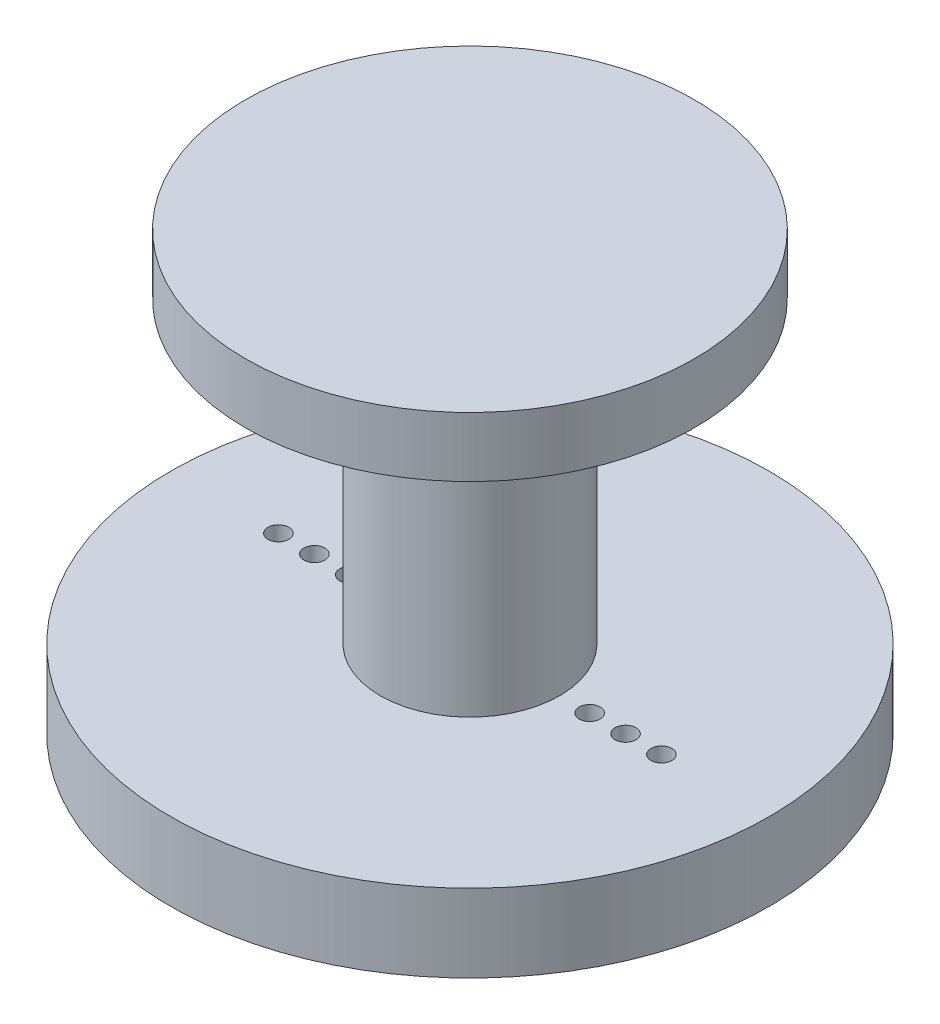
SolidWorks part; units mm, degrees
ref_plane "Front Plane" through (0, 0, 0) normal (0, 0, 1) x (1, 0, 0)
ref_plane "Top Plane" through (0, 0, 0) normal (0, 1, 0) x (1, 0, 0)
ref_plane "Right Plane" through (0, 0, 0) normal (1, 0, 0) x (0, 0, -1)
sketch "Sketch1" plane through (0, 0, 0) normal (0, 1, 0) x (1, 0, 0)
  circle A0 centre (0, 0) radius 25
  dimension "D1" = 50
extrude "Boss-Extrude1" add sketch "Sketch1" along normal blind 6.5 contours A0
sketch "Sketch8" plane through (0, 0, 0) normal (0, -1, 0) x (1, 0, 0)
  line L4 (0, 25) -> (0, -25) construction
  line L5 (-25, 0) -> (25, 0) construction
  circle A4 centre (0, 0) radius 25 construction
  arc A19 (2.8678, 6.2766) -> (8.1035, 4.0243) centre (-3.6427, -16.0687) cw
  arc A20 (8.1035, 4.0243) -> (17.4455, 2.5243) centre (-5.206, -108.7086) cw
  arc A21 (17.4455, 2.5243) -> (21, -0.4757) centre (17.8847, -0.5611) cw
  arc A22 (17.4455, -2.5243) -> (21, -0.4757) centre (18.0512, 0.5327) ccw
  arc A23 (2.8678, -6.2766) -> (8.1035, -4.0243) centre (-3.6427, 16.0687) ccw
  arc A24 (8.1035, -4.0243) -> (17.4455, -2.5243) centre (-5.206, 108.7086) ccw
  arc A25 (2.8678, 6.2766) -> (-2.8678, 6.2766) centre (0, 0) ccw
  arc A26 (-2.8678, -6.2766) -> (2.8678, -6.2766) centre (0, 0) ccw
  arc A27 (-2.8678, 6.2766) -> (-8.1035, 4.0243) centre (3.6427, -16.0687) ccw
  arc A28 (-8.1035, 4.0243) -> (-17.4455, 2.5243) centre (5.206, -108.7086) ccw
  arc A29 (-17.4455, 2.5243) -> (-21, -0.4757) centre (-17.8847, -0.5611) ccw
  arc A30 (-17.4455, -3.4757) -> (-21, -0.4757) centre (-17.8847, -0.3904) cw
  arc A31 (-8.1035, -4.0243) -> (-17.4455, -3.4757) centre (-6.1266, 109.4743) cw
  arc A32 (-2.8678, -6.2766) -> (-8.1035, -4.0243) centre (3.6427, 16.0687) cw
extrude "Horn Hole" cut sketch "Sketch8" against normal blind 2
sketch "Sketch9" plane through (0, 2, 0) normal (0, -1, 0) x (1, 0, 0)
  line L0 (0, 0) -> (7, 0) construction
  line L1 (0, 0) -> (0, -2.0664) construction
  circle A0 centre (7, 0) radius 0.875 construction
  circle A1 centre (10, 0) radius 0.875
  circle A8 centre (13, 0) radius 0.875
  circle A9 centre (16, 0) radius 0.875
  circle A10 centre (-7, 0) radius 0.875 construction
  circle A11 centre (-10, 0) radius 0.875
  circle A12 centre (-13, 0) radius 0.875
  circle A13 centre (-16, 0) radius 0.875
  dimension "D2" = 1.75
  dimension "D1" = 7
  dimension "D3" = 4
extrude "Screw Holes" cut sketch "Sketch9" against normal up to next
sketch "Sketch11" plane through (0, 6.5, 0) normal (0, 1, 0) x (1, 0, 0)
  circle A1 centre (0, 0) radius 7.5
  dimension "D1" = 15
extrude "Boss-Extrude2" add sketch "Sketch11" along normal blind 25
sketch "Sketch12" plane through (0, 31.5, 0) normal (0, 1, 0) x (1, 0, 0)
  circle A0 centre (0, 0) radius 18.75
extrude "Boss-Extrude3" add sketch "Sketch12" along normal blind 5
sketch "Sketch13" plane through (0, 2, 0) normal (0, -1, 0) x (1, 0, 0)
  line L0 (3.4, 0) -> (-3.4, 0)
  arc A0 (3.4, 0) -> (-3.4, 0) centre (0, 0) cw
  point P4 (0, 0)
  dimension "D2" = 3.4
  dimension "D1" = 6.8
revolve "Screw Head Hole" cut sketch "Sketch13" angle 180 about L0 reverse direction yes
